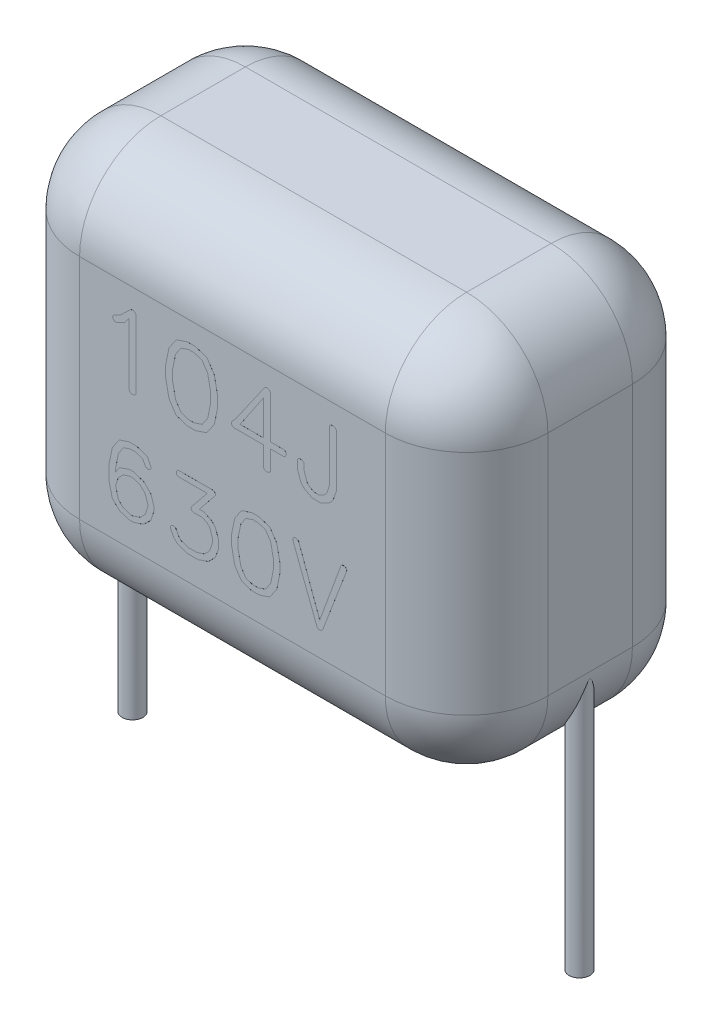
SolidWorks part; units mm, degrees
ref_plane "Front Plane" through (0, 0, 0) normal (0, 0, 1) x (1, 0, 0)
ref_plane "Top Plane" through (0, 0, 0) normal (0, 1, 0) x (1, 0, 0)
ref_plane "Right Plane" through (0, 0, 0) normal (1, 0, 0) x (0, 0, -1)
sketch "Sketch2" plane through (0, 0, 0) normal (1, 0, 0) x (0, 0, -1)
  line L0 (0, 12.4597) -> (0, -8.4662) construction
  line L2 (-1.625, 7.5) -> (1.625, 7.5)
  line L3 (-4.75, 4.375) -> (-4.75, -4.375)
  line L4 (-1.625, -7.5) -> (1.625, -7.5)
  line L5 (4.75, 4.375) -> (4.75, -4.375)
  line L6 (-4.75, 7.5) -> (4.75, -7.5) construction
  line L7 (-4.75, -7.5) -> (4.75, 7.5) construction
  arc A0 (-4.75, -4.375) -> (-1.625, -7.5) centre (-1.625, -4.375) ccw
  arc A1 (4.75, -4.375) -> (1.625, -7.5) centre (1.625, -4.375) cw
  arc A2 (4.75, 4.375) -> (1.625, 7.5) centre (1.625, 4.375) ccw
  arc A3 (-4.75, 4.375) -> (-1.625, 7.5) centre (-1.625, 4.375) cw
  point P3 (0, 0)
  dimension "D3" = 3.125
  dimension "D1" = 15
  dimension "D2" = 9.5
extrude "Boss-Extrude1" add sketch "Sketch2" along normal mid plane 18
fillet "Fillet1" radius 3.125 16 edges at (-9, -7.5, 0) (-9, -6.5847, -3.8347) (-9, 0, -4.75) (-9, 6.5847, -3.8347) (-9, 7.5, 0) (-9, 6.5847, 3.8347) (-9, 0, 4.75) (-9, -6.5847, 3.8347) (9, 0, 4.75) (9, 6.5847, 3.8347) (9, 7.5, 0) (9, 6.5847, -3.8347) (9, 0, -4.75) (9, -6.5847, -3.8347) (9, -7.5, 0) (9, -6.5847, 3.8347)
sketch "Sketch3" plane through (0, 0, 0) normal (0, 0, 1) x (1, 0, 0)
  line L0 (-5.875, 0.875) -> (5.875, 0.875) construction
  line L1 (-5.875, 4.375) -> (-5.875, -4.375) construction
  line L2 (5.875, -4.375) -> (5.875, 4.375) construction
  line L3 (-5.875, -3.375) -> (5.875, -3.375) construction
  line L4 (5.875, -4.375) -> (-5.875, -4.375) construction
  line L5 (5.875, 4.375) -> (-5.875, 4.375) construction
  text T0 "104J" font "SWSimp" height 2.8
  text T1 "630V" font "SWSimp" height 2.6
  dimension "D1" = 1
  dimension "D2" = 3.5
extrude "Boss-Extrude2" add sketch "Sketch3" along normal blind 0.001 from surface starting at face at (0, 0, 4.75)
sketch "Sketch4" plane through (0, 0, 0) normal (0, 1, 0) x (1, 0, 0)
  line L0 (0, 6.5305) -> (0, -6.6049) construction
  line L1 (-9, -1.625) -> (-9, 1.625) construction
  circle A0 centre (-8.59, 0) radius 0.4
  circle A1 centre (8.59, 0) radius 0.4
  dimension "D1" = 0.41
  dimension "D2" = 0.8
extrude "Boss-Extrude3" add sketch "Sketch4" against normal blind 14.5
